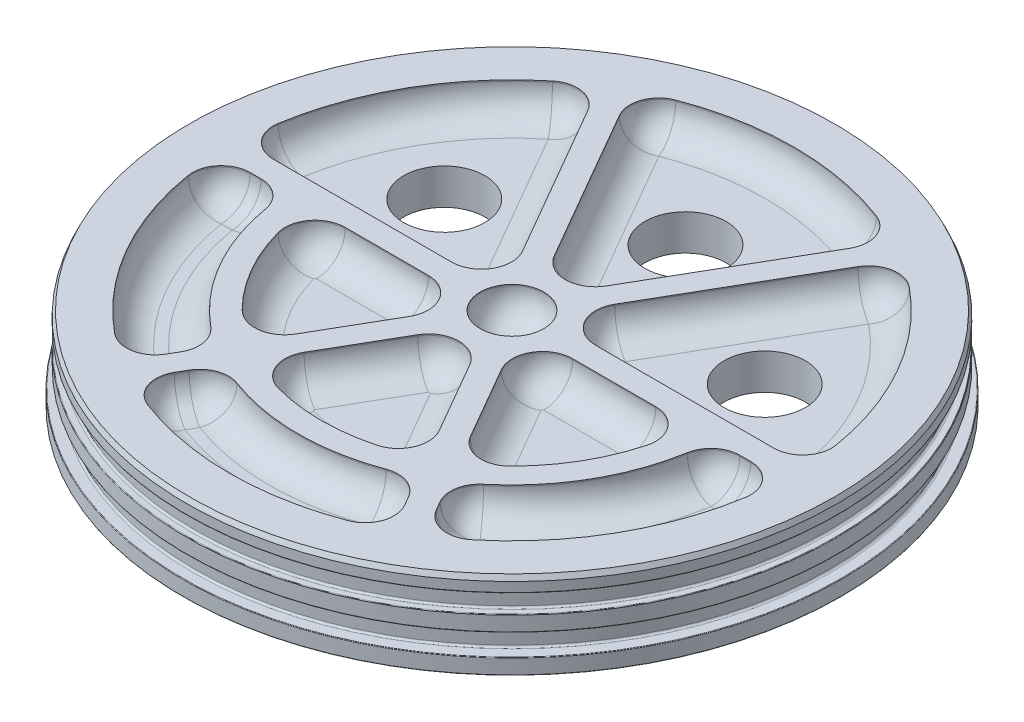
SolidWorks part; units mm, degrees
material "6061-T6 (SS)"
ref_plane "Front Plane" through (0, 0, 0) normal (0, 0, 1) x (1, 0, 0)
ref_plane "Top Plane" through (0, 0, 0) normal (0, 1, 0) x (1, 0, 0)
ref_plane "Right Plane" through (0, 0, 0) normal (1, 0, 0) x (0, 0, -1)
sketch "Sketch1" plane through (0, 0, 0) normal (0, 0, 1) x (1, 0, 0)
  line L0 (0, 48.1922) -> (0, -25.6743) construction
  line L1 (0, 0) -> (72.39, 0)
  line L2 (72.39, 0) -> (72.39, 3.429)
  line L3 (72.39, 3.429) -> (69.6468, 3.429)
  line L4 (69.6468, 3.429) -> (69.6468, 7.493)
  line L5 (69.6468, 7.493) -> (71.4248, 7.493)
  line L6 (71.4248, 7.493) -> (71.4248, 10.922)
  line L7 (71.4248, 10.922) -> (69.6468, 10.922)
  line L8 (62.0268, 18.288) -> (62.0268, 11.684)
  line L9 (62.0268, 11.684) -> (0, 11.684)
  line L10 (0, 11.684) -> (0, 0)
  line L11 (69.6468, 10.922) -> (69.6468, 14.986)
  line L12 (69.6468, 14.986) -> (71.4248, 14.986)
  line L13 (71.4248, 14.986) -> (71.4248, 18.288)
  line L14 (71.4248, 18.288) -> (62.0268, 18.288)
  dimension "D2" = 4.064
  dimension "D5" = 11.684
  dimension "D7" = 4.064
  dimension "D3" = 3.302
  dimension "D4" = 3.429
  dimension "D8" = 7.62
  dimension "D9" = 6.604
  dimension "D1" = 72.39
  dimension "D10" = 1.778
  dimension "D6" = 69.6468
revolve "Revolve1" add sketch "Sketch1" angle 360 about L0
sketch "Sketch6" plane through (0, 0, 0) normal (0, -1, 0) x (1, 0, 0)
  circle A0 centre (0, 0) radius 66.04
  dimension "D1" = 132.08
extrude "Boss-Extrude1" add sketch "Sketch6" along normal blind 2.54
fillet "CNC ID Fillet" radius 0.4064 5 edges at (-69.6468, 7.493, 0) (-69.6468, 3.429, 0) (66.04, 0, 0) (-69.6468, 14.986, 0) (-69.6468, 10.922, 0)
fillet "CNC OD Fillet" radius 0.127 6 edges at (-71.4248, 7.493, 0) (-72.39, 3.429, 0) (-71.4248, 10.922, 0) (-71.4248, 14.986, 0) (66.04, -2.54, 0) (-72.39, 0, 0)
chamfer "CNC Chamfers" distance 0.508 angle 65 1 edges at (-71.4248, 18.288, 0) first distance on face at (-62.0268, 18.288, 0)
hole_wizard "Pipe Tap Drill for 1/2 Tap - Fill Valve" positions "Sketch13" profile "Sketch14" hole size "1/2" standard "ANSI Inch" end condition through all
sketch "Sketch13" plane through (0, -2.54, 0) normal (0, -1, 0) x (-1, 0, 0)
  point P4 (0, 38.1)
  dimension "D1" = 38.1
sketch "Sketch14" plane through (0, -2.54, -38.1) normal (1, 0, 0) x (0, 0, -1)
  line L0 (0, 0) -> (0, 20.828)
  line L1 (0, 20.828) -> (8.9281, 20.828)
  line L2 (8.9281, 20.828) -> (8.9281, 0)
  line L5 (8.9281, 0) -> (0, 0)
  line L11 (0, -6.35) -> (0, 107.95) construction
  dimension "Thru Hole Dia." = 17.8562
  dimension "Thru Hole Depth" = 20.828
hole_wizard "Pipe Tap Drill for 1/4 Tap - Solenoid Valve" positions "Sketch15" profile "Sketch16" hole size "1/2" standard "ANSI Inch" end condition through all
sketch "Sketch15" plane through (0, -2.54, 0) normal (0, -1, 0) x (-1, 0, 0)
  line L2 (-35.1953, 20.32) -> (0, 0) construction
  line L4 (0, 0) -> (0, 38.1) construction
  point P4 (-35.1953, 20.32)
  dimension "D1" = 60
  dimension "D2" = 40.64
sketch "Sketch16" plane through (35.1953, -2.54, -20.32) normal (1, 0, 0) x (0, 0, -1)
  line L0 (0, 0) -> (0, 20.828)
  line L1 (0, 20.828) -> (8.9281, 20.828)
  line L2 (8.9281, 20.828) -> (8.9281, 0)
  line L5 (8.9281, 0) -> (0, 0)
  line L11 (0, -6.35) -> (0, 107.95) construction
  dimension "Thru Hole Dia." = 17.8562
  dimension "Thru Hole Depth" = 20.828
hole_wizard "Pipe Tap Drill for 1/2 Tap - Cryo Valve" positions "Sketch17" profile "Sketch18" hole size "1/2" standard "ANSI Inch" end condition through all
sketch "Sketch17" plane through (0, -2.54, 0) normal (0, -1, 0) x (-1, 0, 0)
  line L2 (35.1953, 20.32) -> (0, 0) construction
  line L5 (0, 0) -> (0, 38.1) construction
  point P4 (35.1953, 20.32)
  dimension "D1" = 60
  dimension "D2" = 40.64
sketch "Sketch18" plane through (-35.1953, -2.54, -20.32) normal (1, 0, 0) x (0, 0, -1)
  line L0 (0, 0) -> (0, 20.828)
  line L1 (0, 20.828) -> (8.9281, 20.828)
  line L2 (8.9281, 20.828) -> (8.9281, 0)
  line L5 (8.9281, 0) -> (0, 0)
  line L11 (0, -6.35) -> (0, 107.95) construction
  dimension "Thru Hole Dia." = 17.8562
  dimension "Thru Hole Depth" = 20.828
sketch "Sketch19" plane through (0, 18.288, 0) normal (0, 1, 0) x (1, 0, 0)
  line L0 (0, 0) -> (31.0134, 53.7168) construction
  line L1 (0, 0) -> (-31.0134, 53.7168) construction
  line L2 (0, 0) -> (62.0268, 0) construction
  line L3 (0, 0) -> (0, 38.1) construction
  line L4 (0, 0) -> (31.0134, -53.7168) construction
  line L5 (0, 0) -> (-31.0134, -53.7168) construction
  line L6 (0, 0) -> (-62.0268, 0) construction
  line L7 (-5.7192, 14.986) -> (-28.8137, 54.9868)
  line L8 (-15.8379, 2.54) -> (-62.0268, 2.54)
  line L9 (-10.1186, -12.446) -> (-19.2504, -28.2626)
  line L10 (5.7192, -14.986) -> (14.851, -30.8026)
  line L11 (15.8379, -2.54) -> (34.1013, -2.54)
  line L12 (10.1186, 12.446) -> (33.2131, 52.4468)
  line L13 (-10.1186, 12.446) -> (-33.2131, 52.4468)
  line L14 (-15.8379, -2.54) -> (-34.1013, -2.54)
  line L15 (-5.7192, -14.986) -> (-14.851, -30.8026)
  line L16 (10.1186, -12.446) -> (23.1162, -34.9584)
  line L17 (15.8379, 2.54) -> (62.0268, 2.54)
  line L18 (5.7192, 14.986) -> (28.8137, 54.9868)
  line L19 (0, -2.54) -> (-62.0268, -2.54) construction
  line L20 (-2.1997, 1.27) -> (-33.2131, -52.4468) construction
  line L21 (-2.1997, -1.27) -> (28.8137, -54.9868) construction
  line L22 (2.1997, -1.27) -> (-28.8137, -54.9868) construction
  line L23 (2.1997, 1.27) -> (33.2131, -52.4468) construction
  line L24 (0, -2.54) -> (62.0268, -2.54) construction
  line L25 (0, 2.54) -> (62.0268, 2.54) construction
  line L26 (2.1997, -1.27) -> (33.2131, 52.4468) construction
  line L27 (-2.1997, 1.27) -> (28.8137, 54.9868) construction
  line L28 (2.1997, 1.27) -> (-28.8137, 54.9868) construction
  line L29 (0, 2.54) -> (-62.0268, 2.54) construction
  line L30 (-2.1997, -1.27) -> (-33.2131, 52.4468) construction
  line L31 (-46.9213, -2.54) -> (-62.0268, -2.54)
  line L32 (46.9213, -2.54) -> (62.0268, -2.54)
  line L35 (-25.6604, -39.365) -> (-33.2131, -52.4468)
  line L36 (-21.2609, -41.905) -> (-28.8137, -54.9868)
  line L37 (21.2609, -41.905) -> (28.8137, -54.9868)
  line L38 (25.6604, -39.365) -> (33.2131, -52.4468)
  circle A0 centre (0, 0) radius 6.985
  circle A2 centre (0, 0) radius 62.0268
  arc A6 (-15.8379, -2.54) -> (-10.1186, -12.446) centre (-15.8379, -9.144) cw
  arc A7 (5.7192, -14.986) -> (-5.7192, -14.986) centre (0, -18.288) ccw
  arc A8 (10.1186, -12.446) -> (15.8379, -2.54) centre (15.8379, -9.144) cw
  arc A9 (15.8379, 2.54) -> (10.1186, 12.446) centre (15.8379, 9.144) cw
  arc A10 (5.7192, 14.986) -> (-5.7192, 14.986) centre (0, 18.288) cw
  arc A11 (-15.8379, 2.54) -> (-10.1186, 12.446) centre (-15.8379, 9.144) ccw
  arc A12 (-44.3774, -2.54) -> (44.3774, -2.54) centre (0, 0) ccw construction
  arc A13 (-46.9213, -2.54) -> (-25.6604, -39.365) centre (0, 0) ccw
  arc A14 (-40.48, -10.8544) -> (-29.6402, -29.6295) centre (0, 0) ccw
  arc A15 (-41.91, 0) -> (41.91, 0) centre (0, 0) ccw construction
  arc A16 (-44.45, 0) -> (44.45, 0) centre (0, 0) ccw construction
  arc A17 (-46.99, 0) -> (46.99, 0) centre (0, 0) ccw construction
  arc A19 (-10.8398, -40.4839) -> (10.8398, -40.4839) centre (0, 0) ccw
  arc A20 (23.1162, -34.9584) -> (40.48, -10.8544) centre (0, 0) ccw
  arc A21 (-21.2609, -41.905) -> (21.2609, -41.905) centre (0, 0) ccw
  arc A22 (25.6604, -39.365) -> (46.9213, -2.54) centre (0, 0) ccw
  arc A23 (-40.48, -10.8544) -> (-34.1013, -2.54) centre (-34.1013, -9.144) cw
  arc A24 (34.1013, -2.54) -> (40.48, -10.8544) centre (34.1013, -9.144) cw
  arc A25 (14.851, -30.8026) -> (10.8398, -40.4839) centre (9.1317, -34.1046) cw
  arc A26 (-10.8398, -40.4839) -> (-14.851, -30.8026) centre (-9.1317, -34.1046) cw
  arc A27 (-29.6402, -29.6295) -> (-19.2504, -28.2626) centre (-24.9696, -24.9606) ccw
  circle A28 centre (0, 0) radius 62.0268 construction
  point P12 (0, 0)
  point P13 (0, 0)
  dimension "D1" = 30
  dimension "D5" = 6.604
  dimension "D8" = 44.45
  dimension "D9" = 6.604
  dimension "D10" = 13.97
  dimension "D2" = 6
  dimension "D3" = 2.54
  dimension "D4" = 2.54
  dimension "D6" = 2.54
  dimension "D7" = 2.54
extrude "Boss-Extrude2" add sketch "Sketch19" against normal up to next
fillet "Fillet2" radius 6.35 61 edges at (-38.9063, 11.684, -2.54) (-10.1186, 11.684, -5.842) (-17.2535, 11.684, -34.9639) (0, 11.684, -11.684) (38.9063, 11.684, -2.54) (10.1186, 11.684, -5.842) (16.6174, 11.684, 23.7022) (10.1186, 11.684, 5.842) (24.9696, 11.684, 2.54) (-10.2851, 11.684, 22.8943) (0, 11.684, 11.684) (10.2851, 11.684, 22.8943) (-24.9696, 11.684, 2.54) (-10.1186, 11.684, 5.842) (-14.6845, 11.684, 20.3543) (-21.6529, 11.684, -32.4239) (17.2535, 11.684, -34.9639) (21.6529, 11.684, -32.4239) (34.0054, 11.684, 24.4965) (0, 11.684, 41.91) (-36.2951, 11.684, 20.955) (39.341, 11.684, 5.1242) (-15.2328, 11.684, 36.6324) (15.2328, 11.684, 36.6324) (-39.341, 11.684, 5.1242) (-24.1082, 11.684, 31.5082) (29.4237, 11.684, 45.8834) (40.6945, 11.684, 23.495) (54.448, 11.684, 2.54) (-25.0243, 11.684, 48.4234) (0, 11.684, 46.99) (25.0243, 11.684, 48.4234) (-54.448, 11.684, 2.54) (-40.6945, 11.684, 23.495) (-29.4237, 11.684, 45.8834) (46.9213, 14.986, 2.54) (25.6604, 14.986, 39.365) (21.2609, 14.986, 41.905) (-21.2609, 14.986, 41.905) (-25.6604, 14.986, 39.365) (-46.9213, 14.986, 2.54) (33.1871, 14.986, 52.4017) (61.9748, 14.986, 2.54) (-28.7877, 14.986, 54.9417) (28.7877, 14.986, 54.9417) (-61.9748, 14.986, 2.54) (-33.1871, 14.986, 52.4017) (-61.9748, 14.986, -2.54) (-33.1871, 14.986, -52.4017) (-28.7877, 14.986, -54.9417) (28.7877, 14.986, -54.9417) (61.9748, 14.986, -2.54) (33.1871, 14.986, -52.4017) (53.7168, 11.684, 31.0134) (0, 11.684, 62.0268) (-53.7168, 11.684, 31.0134) (-53.7168, 11.684, -31.0134) (53.7168, 11.684, -31.0134) (0, 11.684, -62.0268) (6.985, 11.684, 0) (23.1162, 14.986, 34.9584)
sketch "Sketch21" plane through (0, 18.288, 0) normal (0, 1, 0) x (1, 0, 0)
  circle A0 centre (0, 0) radius 66.3169 construction
  text T0 "                                                                                                                                                           RELEVANT EXPERIENCE"
sketch "Sketch22" plane through (0, -2.54, 0) normal (0, -1, 0) x (1, 0, 0)
  line L39 (-29.6809, -46.3289) -> (-10.1186, -12.446)
  line L59 (-15.8379, -2.54) -> (-54.9625, -2.54)
  line L74 (-29.6809, -46.3289) -> (-10.1186, -12.446)
  line L78 (-15.8379, -2.54) -> (-54.9625, -2.54)
  line L82 (-34.1013, 2.54) -> (-15.8379, 2.54)
  line L86 (-10.1186, 12.446) -> (-19.2504, 28.2626)
  line L90 (-34.1013, 2.54) -> (-15.8379, 2.54)
  line L94 (-10.1186, 12.446) -> (-19.2504, 28.2626)
  line L98 (15.8379, 2.54) -> (34.1013, 2.54)
  line L101 (19.4151, 28.548) -> (10.1186, 12.446)
  line L102 (15.8379, 2.54) -> (34.1013, 2.54)
  line L103 (19.4151, 28.548) -> (10.1186, 12.446)
  line L104 (-14.851, 30.8026) -> (-5.7192, 14.986)
  line L105 (5.7192, 14.986) -> (14.851, 30.8026)
  line L106 (-14.851, 30.8026) -> (-5.7192, 14.986)
  line L107 (5.7192, 14.986) -> (14.851, 30.8026)
  line L108 (-28.4967, 44.2777) -> (-29.6809, 46.3289)
  line L109 (-54.9625, 2.54) -> (-52.5939, 2.54)
  line L110 (-28.4967, 44.2777) -> (-29.6809, 46.3289)
  line L111 (-54.9625, 2.54) -> (-52.5939, 2.54)
  line L112 (24.0973, 46.8177) -> (25.2815, 48.8689)
  line L113 (-25.2815, 48.8689) -> (-24.0973, 46.8177)
  line L114 (24.0973, 46.8177) -> (25.2815, 48.8689)
  line L115 (-25.2815, 48.8689) -> (-24.0973, 46.8177)
  line L116 (52.5939, 2.54) -> (54.9625, 2.54)
  line L117 (29.6809, 46.3289) -> (28.4967, 44.2777)
  line L118 (52.5939, 2.54) -> (54.9625, 2.54)
  line L119 (29.6809, 46.3289) -> (28.4967, 44.2777)
  line L120 (10.1186, -12.446) -> (29.6809, -46.3289)
  line L121 (54.9625, -2.54) -> (15.8379, -2.54)
  line L122 (10.1186, -12.446) -> (29.6809, -46.3289)
  line L123 (54.9625, -2.54) -> (15.8379, -2.54)
  line L124 (-5.7192, -14.986) -> (-25.2815, -48.8689)
  line L125 (25.2815, -48.8689) -> (5.7192, -14.986)
  line L126 (-5.7192, -14.986) -> (-25.2815, -48.8689)
  line L127 (25.2815, -48.8689) -> (5.7192, -14.986)
  circle A3 centre (0, 0) radius 6.985
  circle A93 centre (0, 0) radius 6.985
  arc A205 (-61.231, -9.9039) -> (-39.1925, -48.0757) centre (0, 0) ccw
  arc A214 (-39.1925, -48.0757) -> (-29.6809, -46.3289) centre (-35.1802, -43.1539) ccw
  arc A217 (-10.1186, -12.446) -> (-15.8379, -2.54) centre (-15.8379, -9.144) ccw
  arc A229 (-54.9625, -2.54) -> (-61.231, -9.9039) centre (-54.9625, -8.89) ccw
  arc A241 (-61.231, -9.9039) -> (-39.1925, -48.0757) centre (0, 0) ccw
  arc A267 (-39.1925, -48.0757) -> (-29.6809, -46.3289) centre (-35.1802, -43.1539) ccw
  arc A268 (-10.1186, -12.446) -> (-15.8379, -2.54) centre (-15.8379, -9.144) ccw
  arc A269 (-54.9625, -2.54) -> (-61.231, -9.9039) centre (-54.9625, -8.89) ccw
  arc A270 (-19.2504, 28.2626) -> (-29.6402, 29.6295) centre (-24.9696, 24.9606) ccw
  arc A271 (-29.6402, 29.6295) -> (-40.48, 10.8544) centre (0, 0) ccw
  arc A272 (-40.48, 10.8544) -> (-34.1013, 2.54) centre (-34.1013, 9.144) ccw
  arc A273 (-15.8379, 2.54) -> (-10.1186, 12.446) centre (-15.8379, 9.144) ccw
  arc A274 (-19.2504, 28.2626) -> (-29.6402, 29.6295) centre (-24.9696, 24.9606) ccw
  arc A275 (-29.6402, 29.6295) -> (-40.48, 10.8544) centre (0, 0) ccw
  arc A276 (-40.48, 10.8544) -> (-34.1013, 2.54) centre (-34.1013, 9.144) ccw
  arc A277 (-15.8379, 2.54) -> (-10.1186, 12.446) centre (-15.8379, 9.144) ccw
  arc A278 (34.1013, 2.54) -> (40.48, 10.8544) centre (34.1013, 9.144) ccw
  arc A279 (40.48, 10.8544) -> (29.3634, 29.9039) centre (0, 0) ccw
  arc A280 (29.3634, 29.9039) -> (19.4151, 28.548) centre (24.9144, 25.373) ccw
  arc A281 (10.1186, 12.446) -> (15.8379, 2.54) centre (15.8379, 9.144) ccw
  arc A282 (34.1013, 2.54) -> (40.48, 10.8544) centre (34.1013, 9.144) ccw
  arc A283 (40.48, 10.8544) -> (29.3634, 29.9039) centre (0, 0) ccw
  arc A284 (29.3634, 29.9039) -> (19.4151, 28.548) centre (24.9144, 25.373) ccw
  arc A285 (10.1186, 12.446) -> (15.8379, 2.54) centre (15.8379, 9.144) ccw
  arc A286 (10.8398, 40.4839) -> (-10.8398, 40.4839) centre (0, 0) ccw
  arc A287 (-10.8398, 40.4839) -> (-14.851, 30.8026) centre (-9.1317, 34.1046) ccw
  arc A288 (-5.7192, 14.986) -> (5.7192, 14.986) centre (0, 18.288) ccw
  arc A289 (14.851, 30.8026) -> (10.8398, 40.4839) centre (9.1317, 34.1046) ccw
  arc A290 (10.8398, 40.4839) -> (-10.8398, 40.4839) centre (0, 0) ccw
  arc A291 (-10.8398, 40.4839) -> (-14.851, 30.8026) centre (-9.1317, 34.1046) ccw
  arc A292 (-5.7192, 14.986) -> (5.7192, 14.986) centre (0, 18.288) ccw
  arc A293 (14.851, 30.8026) -> (10.8398, 40.4839) centre (9.1317, 34.1046) ccw
  arc A296 (29.6809, -46.3289) -> (39.1925, -48.0757) centre (35.1802, -43.1539) ccw
  arc A297 (39.1925, -48.0757) -> (61.231, -9.9039) centre (0, 0) ccw
  arc A298 (-29.9488, 36.2095) -> (-46.3328, 7.8317) centre (0, 0) ccw
  arc A299 (-29.9488, 36.2095) -> (-28.4967, 44.2777) centre (-33.9959, 41.1027) ccw
  arc A300 (-29.6809, 46.3289) -> (-39.1925, 48.0757) centre (-35.1802, 43.1539) ccw
  arc A301 (-39.1925, 48.0757) -> (-61.231, 9.9039) centre (0, 0) ccw
  arc A302 (-61.231, 9.9039) -> (-54.9625, 2.54) centre (-54.9625, 8.89) ccw
  arc A303 (-52.5939, 2.54) -> (-46.3328, 7.8317) centre (-52.5939, 8.89) ccw
  arc A304 (-29.9488, 36.2095) -> (-46.3328, 7.8317) centre (0, 0) ccw
  arc A305 (-29.9488, 36.2095) -> (-28.4967, 44.2777) centre (-33.9959, 41.1027) ccw
  arc A306 (-29.6809, 46.3289) -> (-39.1925, 48.0757) centre (-35.1802, 43.1539) ccw
  arc A307 (-39.1925, 48.0757) -> (-61.231, 9.9039) centre (0, 0) ccw
  arc A308 (-61.231, 9.9039) -> (-54.9625, 2.54) centre (-54.9625, 8.89) ccw
  arc A309 (-52.5939, 2.54) -> (-46.3328, 7.8317) centre (-52.5939, 8.89) ccw
  arc A310 (16.384, 44.0412) -> (-16.384, 44.0412) centre (0, 0) ccw
  arc A311 (16.384, 44.0412) -> (24.0973, 46.8177) centre (18.598, 49.9927) ccw
  arc A312 (25.2815, 48.8689) -> (22.0385, 57.9796) centre (19.7823, 52.0439) ccw
  arc A313 (22.0385, 57.9796) -> (-22.0385, 57.9796) centre (0, 0) ccw
  arc A314 (-22.0385, 57.9796) -> (-25.2815, 48.8689) centre (-19.7823, 52.0439) ccw
  arc A315 (-24.0973, 46.8177) -> (-16.384, 44.0412) centre (-18.598, 49.9927) ccw
  arc A316 (16.384, 44.0412) -> (-16.384, 44.0412) centre (0, 0) ccw
  arc A317 (16.384, 44.0412) -> (24.0973, 46.8177) centre (18.598, 49.9927) ccw
  arc A318 (25.2815, 48.8689) -> (22.0385, 57.9796) centre (19.7823, 52.0439) ccw
  arc A319 (22.0385, 57.9796) -> (-22.0385, 57.9796) centre (0, 0) ccw
  arc A320 (-22.0385, 57.9796) -> (-25.2815, 48.8689) centre (-19.7823, 52.0439) ccw
  arc A321 (-24.0973, 46.8177) -> (-16.384, 44.0412) centre (-18.598, 49.9927) ccw
  arc A322 (46.3328, 7.8317) -> (29.9488, 36.2095) centre (0, 0) ccw
  arc A323 (46.3328, 7.8317) -> (52.5939, 2.54) centre (52.5939, 8.89) ccw
  arc A324 (54.9625, 2.54) -> (61.231, 9.9039) centre (54.9625, 8.89) ccw
  arc A325 (61.231, 9.9039) -> (39.1925, 48.0757) centre (0, 0) ccw
  arc A326 (39.1925, 48.0757) -> (29.6809, 46.3289) centre (35.1802, 43.1539) ccw
  arc A327 (28.4967, 44.2777) -> (29.9488, 36.2095) centre (33.9959, 41.1027) ccw
  arc A328 (46.3328, 7.8317) -> (29.9488, 36.2095) centre (0, 0) ccw
  arc A329 (46.3328, 7.8317) -> (52.5939, 2.54) centre (52.5939, 8.89) ccw
  arc A330 (54.9625, 2.54) -> (61.231, 9.9039) centre (54.9625, 8.89) ccw
  arc A331 (61.231, 9.9039) -> (39.1925, 48.0757) centre (0, 0) ccw
  arc A332 (39.1925, 48.0757) -> (29.6809, 46.3289) centre (35.1802, 43.1539) ccw
  arc A333 (28.4967, 44.2777) -> (29.9488, 36.2095) centre (33.9959, 41.1027) ccw
  arc A334 (61.231, -9.9039) -> (54.9625, -2.54) centre (54.9625, -8.89) ccw
  arc A335 (15.8379, -2.54) -> (10.1186, -12.446) centre (15.8379, -9.144) ccw
  arc A336 (29.6809, -46.3289) -> (39.1925, -48.0757) centre (35.1802, -43.1539) ccw
  arc A337 (39.1925, -48.0757) -> (61.231, -9.9039) centre (0, 0) ccw
  arc A338 (61.231, -9.9039) -> (54.9625, -2.54) centre (54.9625, -8.89) ccw
  arc A339 (15.8379, -2.54) -> (10.1186, -12.446) centre (15.8379, -9.144) ccw
  arc A340 (-25.2815, -48.8689) -> (-22.0385, -57.9796) centre (-19.7823, -52.0439) ccw
  arc A341 (-22.0385, -57.9796) -> (22.0385, -57.9796) centre (0, 0) ccw
  arc A342 (22.0385, -57.9796) -> (25.2815, -48.8689) centre (19.7823, -52.0439) ccw
  arc A343 (5.7192, -14.986) -> (-5.7192, -14.986) centre (0, -18.288) ccw
  arc A344 (-25.2815, -48.8689) -> (-22.0385, -57.9796) centre (-19.7823, -52.0439) ccw
  arc A345 (-22.0385, -57.9796) -> (22.0385, -57.9796) centre (0, 0) ccw
  arc A346 (22.0385, -57.9796) -> (25.2815, -48.8689) centre (19.7823, -52.0439) ccw
  arc A347 (5.7192, -14.986) -> (-5.7192, -14.986) centre (0, -18.288) ccw
  dimension "D1" = 0
  dimension "D2" = 0
  dimension "D3" = 0
  dimension "D4" = 0
  dimension "D5" = 0
  dimension "D6" = 0
  dimension "D7" = 0
  dimension "D8" = 0
  dimension "D9" = 0
  dimension "D10" = 0
extrude "Cut-Extrude1" cut sketch "Sketch22" against normal blind 6.35
fillet "Fillet3" radius 6.35 61 edges at (59.7978, 3.81, -4.7739) (53.7168, 3.81, -31.0134) (34.0332, 3.81, -49.3995) (19.8998, 3.81, -29.3875) (10.1186, 3.81, -5.842) (-10.1186, 3.81, -5.842) (-19.8998, 3.81, -29.3875) (-34.0332, 3.81, -49.3995) (-53.7168, 3.81, -31.0134) (-59.7978, 3.81, -4.7739) (0, 3.81, -11.684) (15.5004, 3.81, -31.9275) (25.7646, 3.81, -54.1734) (0, 3.81, -62.0268) (-25.7646, 3.81, -54.1734) (-40.6945, 3.81, 23.495) (-48.495, 3.81, 4.0401) (-53.7782, 3.81, 2.54) (-59.7978, 3.81, 4.7739) (-53.7168, 3.81, 31.0134) (-34.0332, 3.81, 49.3995) (-29.0888, 3.81, 45.3033) (-27.7464, 3.81, 39.9779) (0, 3.81, 46.99) (-20.7487, 3.81, 44.018) (-24.6894, 3.81, 47.8433) (-25.7646, 3.81, 54.1734) (0, 3.81, 62.0268) (25.7646, 3.81, 54.1734) (24.6894, 3.81, 47.8433) (20.7487, 3.81, 44.018) (40.6945, 3.81, 23.495) (27.7464, 3.81, 39.9779) (29.0888, 3.81, 45.3033) (34.0332, 3.81, 49.3995) (53.7168, 3.81, 31.0134) (59.7978, 3.81, 4.7739) (53.7782, 3.81, 2.54) (48.495, 3.81, 4.0401) (14.7669, 3.81, 20.497) (24.0568, 3.81, 31.6648) (36.1973, 3.81, 21.1235) (39.341, 3.81, 5.1242) (24.9696, 3.81, 2.54) (10.1186, 3.81, 5.842) (10.2851, 3.81, 22.8943) (0, 3.81, 11.684) (-10.2851, 3.81, 22.8943) (-15.2328, 3.81, 36.6324) (0, 3.81, 41.91) (15.2328, 3.81, 36.6324) (-10.1186, 3.81, 5.842) (-24.9696, 3.81, 2.54) (-39.341, 3.81, 5.1242) (-36.2951, 3.81, 20.955) (-24.1082, 3.81, 31.5082) (-14.6845, 3.81, 20.3543) (6.985, 3.81, 0) (35.4002, 3.81, -2.54) (-35.4002, 3.81, -2.54) (-15.5004, 3.81, -31.9275)
sketch "Sketch20" plane through (0, 3.81, 0) normal (0, -1, 0) x (-1, 0, 0)
  line L0 (0, 0) -> (-35.1953, 20.32) construction
  line L1 (-40.2753, 11.5212) -> (-30.1153, 29.1188) construction
  line L2 (-11.43, 38.1) -> (11.43, 38.1) construction
  line L3 (0, 0) -> (0, 38.1) construction
  line L4 (40.2753, 11.5212) -> (30.1153, 29.1188) construction
  line L5 (0, 0) -> (35.1953, 20.32) construction
  arc A1 (11.43, 38.1) -> (-11.43, 38.1) centre (0, 38.1) ccw construction
  arc A2 (11.43, 38.1) -> (-11.43, 38.1) centre (0, 38.1) cw construction
  arc A3 (-40.2753, 11.5212) -> (-30.1153, 29.1188) centre (-35.1953, 20.32) ccw construction
  arc A4 (-40.2753, 11.5212) -> (-30.1153, 29.1188) centre (-35.1953, 20.32) cw construction
  arc A5 (40.2753, 11.5212) -> (30.1153, 29.1188) centre (35.1953, 20.32) ccw construction
  arc A6 (40.2753, 11.5212) -> (30.1153, 29.1188) centre (35.1953, 20.32) cw construction
  text T1 "FILL" font "Century Gothic" height in points 20
  text T3 "INJECTOR" font "Century Gothic" height in points 12
  text T4 "DUMP" font "Century Gothic" height in points 14
  point P14 (-35.1953, 20.32)
  dimension "D1" = 11.43
  dimension "D2" = 10.16
sketch "Sketch24" plane through (0, -2.54, 0) normal (0, -1, 0) x (1, 0, 0)
  arc A0 (-42.672, 0) -> (42.672, 0) centre (0, 0) cw construction
  text T0 "THIS SIDE OUT" font "Century Gothic" height in points 12
  dimension "D1" = 42.672
equation "\"D6@Sketch1\"=5.484/2"
equation "\"D1@Sketch1\"=5.7/2"
